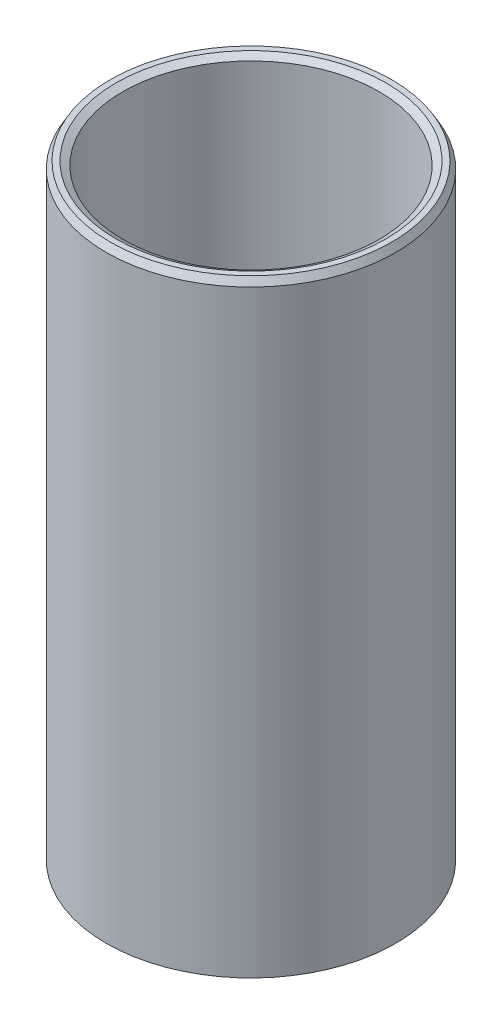
SolidWorks part; units mm, degrees
ref_plane "Front Plane" through (0, 0, 0) normal (0, 0, 1) x (1, 0, 0)
ref_plane "Top Plane" through (0, 0, 0) normal (0, 1, 0) x (1, 0, 0)
ref_plane "Right Plane" through (0, 0, 0) normal (1, 0, 0) x (0, 0, -1)
sketch "Sketch1" plane through (0, 0, 0) normal (0, 1, 0) x (1, 0, 0)
  circle A0 centre (0, 0) radius 37.5
  dimension "SLEEVE_OD" = 75
extrude "Boss-Extrude1" add sketch "Sketch1" along normal blind 157.8595
sketch "Sketch2" plane through (0, 0, 0) normal (0, 1, 0) x (1, 0, 0)
  circle A0 centre (0, 0) radius 33.187
  dimension "BORE_D" = 66.3739
extrude "Cut-Extrude1" cut sketch "Sketch2" along normal through all
chamfer "Chamfer1" distance 1.8039 angle 30 4 edges at (0, 157.8595, 33.187) (0, 0, 33.187) (0, 0, 37.5) (0, 157.8595, 37.5) first distance on face at (0, 157.8595, 33.187) first distance on face at (0, 0, 33.187) first distance on face at (0, 157.8595, 37.5)
